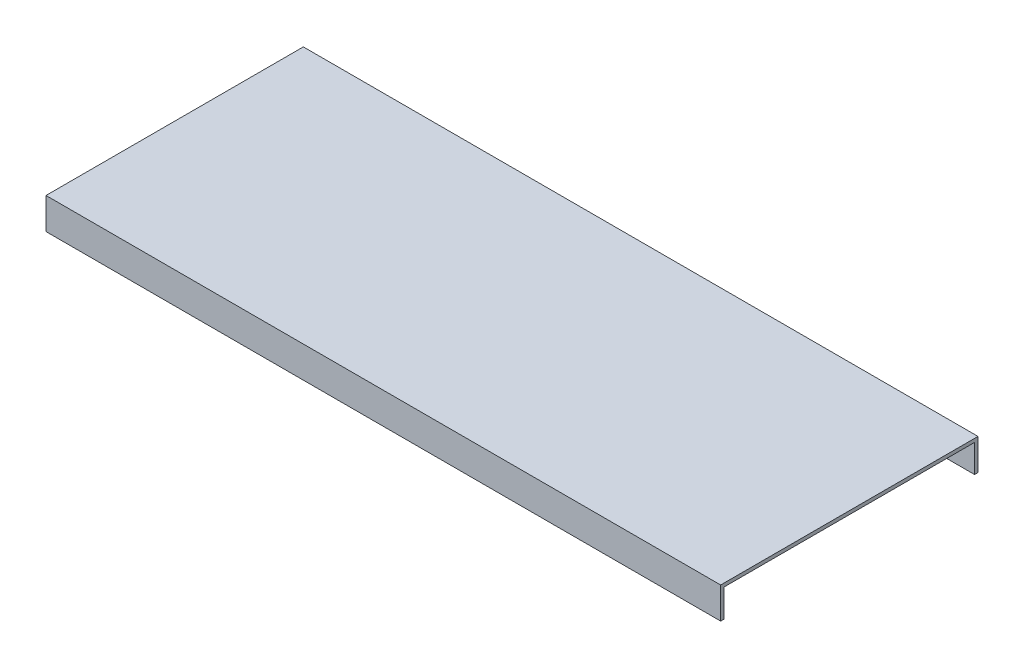
SolidWorks part; units mm, degrees
material "ASTM A36 Steel"
ref_plane "Front Plane" through (0, 0, 0) normal (0, 0, 1) x (1, 0, 0)
ref_plane "Top Plane" through (0, 0, 0) normal (0, 1, 0) x (1, 0, 0)
ref_plane "Right Plane" through (0, 0, 0) normal (1, 0, 0) x (0, 0, -1)
sketch "Sketch1" plane through (0, 0, 0) normal (0, 1, 0) x (1, 0, 0)
  line L1 (153.9875, 58.7375) -> (-153.9875, 58.7375)
  line L2 (153.9875, 58.7375) -> (153.9875, -58.7375)
  line L3 (153.9875, -58.7375) -> (-153.9875, -58.7375)
  line L4 (-153.9875, 58.7375) -> (-153.9875, -58.7375)
  line L5 (153.9875, 58.7375) -> (-153.9875, -58.7375) construction
  line L6 (153.9875, -58.7375) -> (-153.9875, 58.7375) construction
  point P0 (0, 0)
  dimension "D1" = 307.975
  dimension "D2" = 117.475
extrude "Boss-Extrude1" add sketch "Sketch1" along normal blind 1.5875
sketch "Sketch2" plane through (0, 0, 0) normal (0, -1, 0) x (1, 0, 0)
  line L4 (152.4, 57.15) -> (153.9875, 57.15)
  line L5 (152.4, -57.15) -> (153.9875, -57.15)
  line L8 (-152.4, 57.15) -> (-152.4, -57.15)
  line L9 (-152.4, -57.15) -> (152.4, -57.15)
  line L10 (152.4, -57.15) -> (152.4, 57.15)
  line L11 (152.4, 57.15) -> (-152.4, 57.15)
  line L12 (-152.4, 57.15) -> (-152.4, -57.15)
  line L13 (-152.4, -57.15) -> (152.4, -57.15)
  line L14 (152.4, -57.15) -> (152.4, 57.15)
  line L15 (152.4, 57.15) -> (-152.4, 57.15)
  line L16 (-153.9875, 58.7375) -> (-153.9875, -58.7375)
  line L17 (-153.9875, -58.7375) -> (153.9875, -58.7375)
  line L18 (153.9875, -58.7375) -> (153.9875, 58.7375)
  line L19 (153.9875, 58.7375) -> (-153.9875, 58.7375)
  line L20 (-153.9875, 58.7375) -> (-153.9875, -58.7375)
  line L21 (-153.9875, -58.7375) -> (153.9875, -58.7375)
  line L22 (153.9875, -58.7375) -> (153.9875, 58.7375)
  line L23 (153.9875, 58.7375) -> (-153.9875, 58.7375)
  line M9 (-153.9875, 58.7375) -> (-153.9875, -58.7375)
  line M10 (-153.9875, -58.7375) -> (153.9875, -58.7375)
  line M11 (153.9875, -58.7375) -> (153.9875, 58.7375)
  line M12 (153.9875, 58.7375) -> (-153.9875, 58.7375)
  dimension "D1" = 1.5875
  dimension "D2" = 0
extrude "Boss-Extrude2" add sketch "Sketch2" along normal blind 12.7 contours L15 L4 L5 L13 L12 M11 M12 M9 M10 region at (0, 0, 57.4796)
